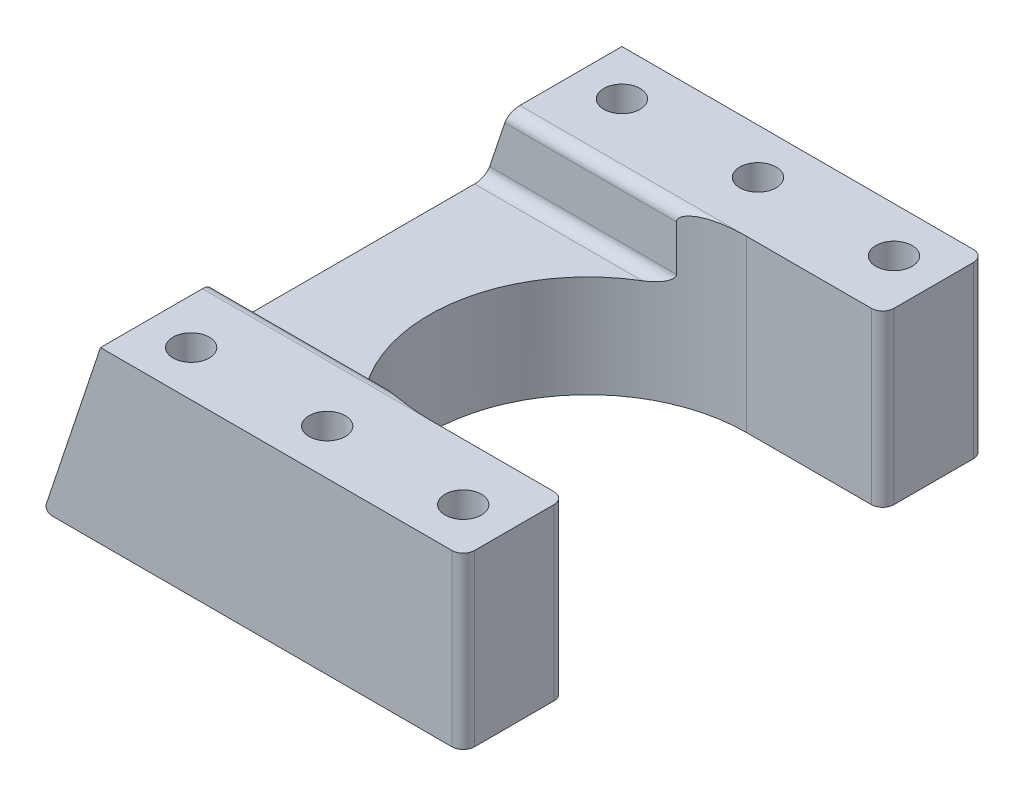
SolidWorks part; units mm, degrees
material "PEI"
ref_plane "Front Plane" through (0, 0, 0) normal (0, 0, 1) x (1, 0, 0)
ref_plane "Top Plane" through (0, 0, 0) normal (0, 1, 0) x (1, 0, 0)
ref_plane "Right Plane" through (0, 0, 0) normal (1, 0, 0) x (0, 0, -1)
sketch "Sketch2" plane through (0, 0, 0) normal (0, 1, 0) x (1, 0, 0)
  line L0 (0, 0) -> (0, 19)
  line L1 (0, 0) -> (-12, 0)
  line L2 (-12, 0) -> (-12, 19)
  line L3 (0, 0) -> (4, 0)
  line L4 (16, -23) -> (-16, -23)
  line L5 (16, -23) -> (16, 23)
  line L6 (16, 23) -> (-16, 23)
  line L7 (-16, -23) -> (-16, 23)
  line L8 (16, -23) -> (-16, 23) construction
  line L9 (16, 23) -> (-16, -23) construction
  line L10 (4, 14) -> (16, 14)
  line L11 (4, -14) -> (16, -14)
  circle A0 centre (-12, 19) radius 1.6
  circle A1 centre (0, 19) radius 1.6
  circle A2 centre (12, 19) radius 1.6
  circle A3 centre (12, -19) radius 1.6
  circle A4 centre (0, -19) radius 1.6
  circle A5 centre (-12, -19) radius 1.6
  circle A6 centre (4, 0) radius 14
  dimension "D3" = 3.2
  dimension "D4" = 3.2
  dimension "D7" = 28
  dimension "D1" = 12
  dimension "D2" = 19
  dimension "D5" = 19
  dimension "D6" = 4
  dimension "D8" = 46
  dimension "D9" = 32
extrude "Boss-Extrude1" add sketch "Sketch2" along normal blind 15 contours A6 L5 L6 L7 L4 A0 A1 A4 A3 A2 A5 region at (-7.6743, 0, -8.7015)
sketch "Sketch4" plane through (0, 0, 23) normal (0, 0, 1) x (1, 0, 0)
  line L0 (-16, 0) -> (-21, 0)
  line L1 (-21, 0) -> (-16, 15)
  line L4 (-16, 0) -> (16, 0)
  line L5 (16, 0) -> (16, 15)
  line L6 (16, 15) -> (-16, 15)
  line L7 (-16, 15) -> (-16, 0)
  line L8 (-16, 0) -> (16, 0)
  line L9 (16, 0) -> (16, 15)
  line L10 (16, 15) -> (-16, 15)
  line L11 (-16, 15) -> (-16, 0)
  line M9 (-16, 15) -> (-16, 0)
  dimension "D2" = 5
  dimension "D1" = 0
extrude "Boss-Extrude2" add sketch "Sketch4" against normal up to surface (46 mm away) contours L1 L0 M9 region at (-17.6667, 5, 23) up to face at (0, 7.5, -23)
sketch "Sketch5" plane through (0, 15, 0) normal (0, 1, 0) x (1, 0, 0)
  line L0 (0, 0) -> (-21, 0)
  line L1 (0, 13) -> (-21, 13)
  line L2 (0, -13) -> (-21, -13)
  line L4 (-16, -23) -> (-16, 23)
  line L5 (-16, 23) -> (-21, 23)
  line L6 (-21, 23) -> (-21, -23)
  line L7 (-21, -23) -> (-16, -23)
  line L8 (-16, -23) -> (-16, 23)
  line L9 (-16, 23) -> (-21, 23)
  line L10 (-21, 23) -> (-21, -23)
  line L11 (-21, -23) -> (-16, -23)
  line L15 (4, 14) -> (16, 14)
  line L16 (16, 14) -> (16, 23)
  line L17 (16, 23) -> (-16, 23)
  line L18 (-16, 23) -> (-16, -23)
  line L19 (-16, -23) -> (16, -23)
  line L20 (16, -23) -> (16, -14)
  line L21 (16, -14) -> (4, -14)
  line L22 (4, 14) -> (16, 14)
  line L23 (16, 14) -> (16, 23)
  line L24 (16, 23) -> (-16, 23)
  line L25 (-16, 23) -> (-16, -23)
  line L26 (-16, -23) -> (16, -23)
  line L27 (16, -23) -> (16, -14)
  line L28 (16, -14) -> (4, -14)
  arc A1 (4, 14) -> (4, -14) centre (4, 0) ccw
  arc A2 (4, 14) -> (4, -14) centre (4, 0) ccw
  arc M16 (4, -14) -> (4, 14) centre (4, 0) cw
  line M20 (-16, 23) -> (-16, -23)
  dimension "D1" = 0
  dimension "D2" = 0
  dimension "D3" = 13
  dimension "D4" = 13
extrude "Cut-Extrude1" cut sketch "Sketch5" against normal blind 6 contours L1 L0 M16 M20 | L1 L10 L0 M20 | L2 L0 M16 M20 | L0 L10 L2 M20 region at (-11.4463, 15, 7.5042) region at (-11.4463, 15, -7.5042) region at (-18.5, 15, 6.5) region at (-18.5, 15, -6.5)
fillet "Fillet1" radius 1 4 edges at (-9.5981, 9, 13) (-9.5981, 9, -13) (-8.5981, 15, 13) (-8.5981, 15, -13)
fillet "Fillet2" radius 0.5 1 edges at (-21, 0, 0)
fillet "Fillet3" radius 1 4 edges at (16, 7.5, -23) (16, 7.5, -14) (16, 7.5, 14) (16, 7.5, 23)
